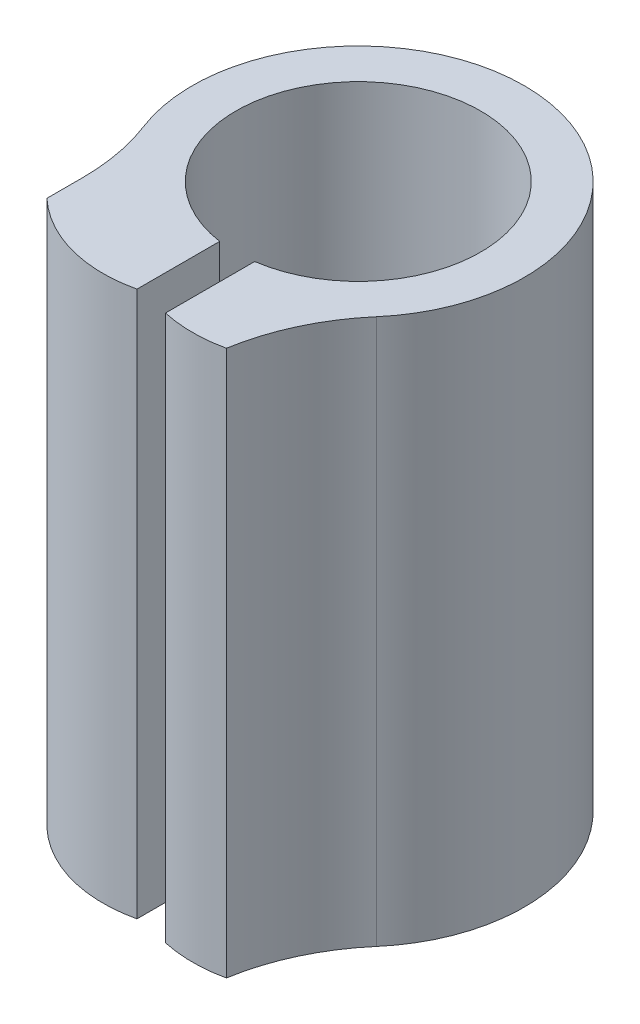
SolidWorks part; units mm, degrees
ref_plane "Front Plane" through (0, 0, 0) normal (0, 0, 1) x (1, 0, 0)
ref_plane "Top Plane" through (0, 0, 0) normal (0, 1, 0) x (1, 0, 0)
ref_plane "Right Plane" through (0, 0, 0) normal (1, 0, 0) x (0, 0, -1)
sketch "Sketch1" plane through (0, 0, 0) normal (0, 1, 0) x (1, 0, 0)
  line L0 (0, -10.091) -> (0, -16.8892) construction
  line L1 (2.5, -14.0798) -> (2.5, -21.0065)
  line L2 (2.5, -17.5431) -> (0, -17.5431) construction
  line L3 (-2.5, -14.0798) -> (-2.5, -21.0065)
  line L4 (2.5, -21.0065) -> (2.5, -30.0765)
  line L5 (2.5, -30.0765) -> (11.22, -30.0765) construction
  line L6 (11.22, -30.0765) -> (11.22, -20.9326)
  line L8 (-2.5, -21.0065) -> (-2.5, -29.1482)
  line L10 (-20.19, -24.34) -> (-20.19, -12.5071)
  arc A0 (11.22, -20.9326) -> (-20.19, -12.5071) centre (0, 0) ccw
  arc A1 (2.5, -14.0798) -> (-2.5, -14.0798) centre (0, 0) ccw
  arc A2 (2.5, -30.0765) -> (11.22, -30.0765) centre (6.86, -10.2433) ccw
  arc A3 (-2.5, -29.1482) -> (-20.19, -24.34) centre (-6.86, -10.2433) cw
  dimension "D1" = 2.5
  dimension "D5" = 23.75
  dimension "D6" = 20.3067
  dimension "D7" = 14.3
  dimension "D2" = 6.9267
  dimension "D3" = 8.72
  dimension "D4" = 9.07
  dimension "D8" = 17.69
  dimension "D9" = 9.1439
  dimension "D10" = 11.8329
extrude "Boss-Extrude1" add sketch "Sketch1" along normal blind 78
ref_plane "Plane1" through (0, 78, 0) normal (0, 1, 0) x (1, 0, 0)
sketch "Sketch2" plane through (0, 78, 0) normal (0, 1, 0) x (1, 0, 0)
  circle A0 centre (0, 0) radius 17.5
extrude "Cut-Extrude1" cut sketch "Sketch2" against normal blind 39
fillet "Fillet1" radius 30 2 edges at (11.22, 39, 20.9326) (-20.19, 39, 12.5071)
